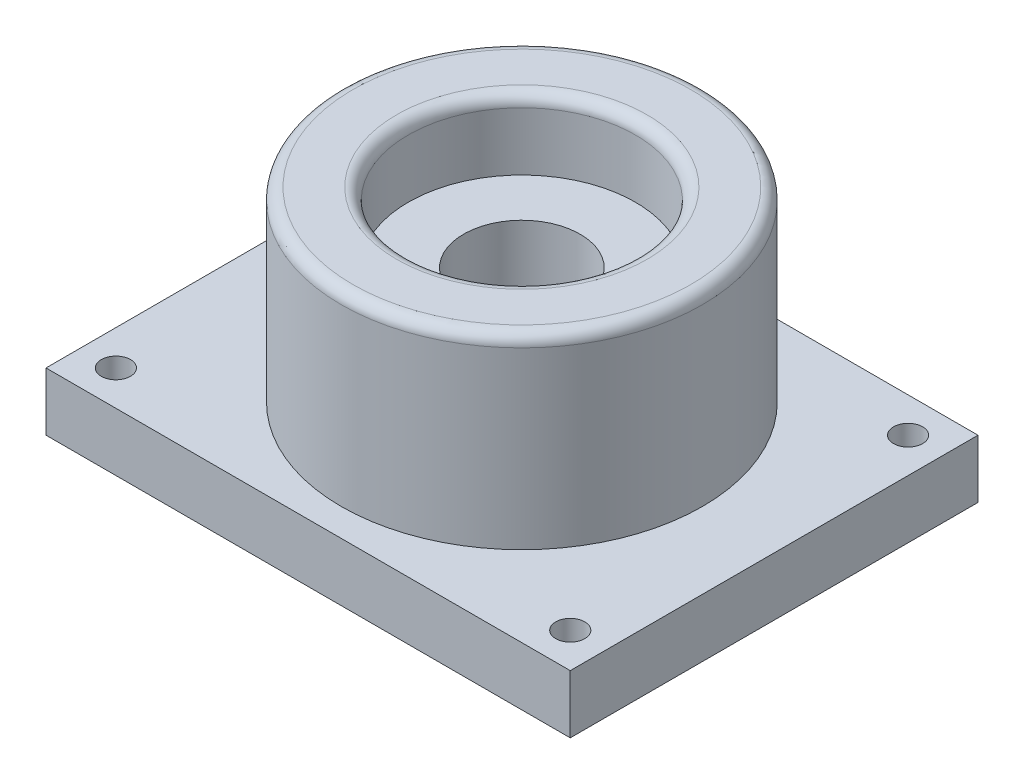
SolidWorks part; units mm, degrees
ref_plane "Front Plane" through (0, 0, 0) normal (0, 0, 1) x (1, 0, 0)
ref_plane "Top Plane" through (0, 0, 0) normal (0, 1, 0) x (1, 0, 0)
ref_plane "Right Plane" through (0, 0, 0) normal (1, 0, 0) x (0, 0, -1)
sketch "Sketch1" plane through (0, 0, 0) normal (0, 1, 0) x (1, 0, 0)
  circle A0 centre (0, 0) radius 15.5
  dimension "D1" = 31
extrude "Boss-Extrude1" add sketch "Sketch1" along normal blind 16
ref_plane "Plane1" through (0, 0, 0) normal (0, -1, 0) x (-1, 0, 0)
sketch "Sketch16" plane through (0, 0, 0) normal (0, -1, 0) x (1, 0, 0)
  line L0 (0, 0) -> (22.0242, 17.8701) construction
  line L1 (-22.9758, 17.8701) -> (22.0242, 17.8701)
  line L2 (-22.9758, 17.8701) -> (-22.9758, -17.1299)
  line L3 (-22.9758, -17.1299) -> (22.0242, -17.1299)
  line L4 (22.0242, 17.8701) -> (22.0242, -17.1299)
  line L5 (-22.9758, 17.8701) -> (22.0242, -17.1299) construction
  circle A0 centre (-19.9758, -14.1299) radius 1.25
  circle A4 centre (19.0242, -14.1299) radius 1.25
  circle A5 centre (19.0242, 14.8701) radius 1.25
  circle A6 centre (-19.9758, 14.8701) radius 1.25
  point P0 (0, 0)
  dimension "D3" = 2.5
  dimension "D5" = 3
  dimension "D1" = 35
  dimension "D2" = 45
  dimension "D4" = 3
  dimension "D6" = 2
  dimension "D7" = 2
extrude "Boss-Extrude6" add sketch "Sketch16" along normal blind 5
sketch "Sketch17" plane through (0, 16, 0) normal (0, 1, 0) x (1, 0, 0)
  circle A0 centre (0, 0) radius 9.75
  dimension "D1" = 19.5
extrude "Cut-Extrude5" cut sketch "Sketch17" against normal blind 6
sketch "Sketch18" plane through (0, 10, 0) normal (0, 1, 0) x (1, 0, 0)
  circle A0 centre (0, 0) radius 5
  dimension "D1" = 10
extrude "Cut-Extrude7" cut sketch "Sketch18" against normal blind 19
fillet "Fillet1" radius 1 1 edges at (0, 16, 9.75)
fillet "Fillet3" radius 1 1 edges at (0, 16, 15.5)
